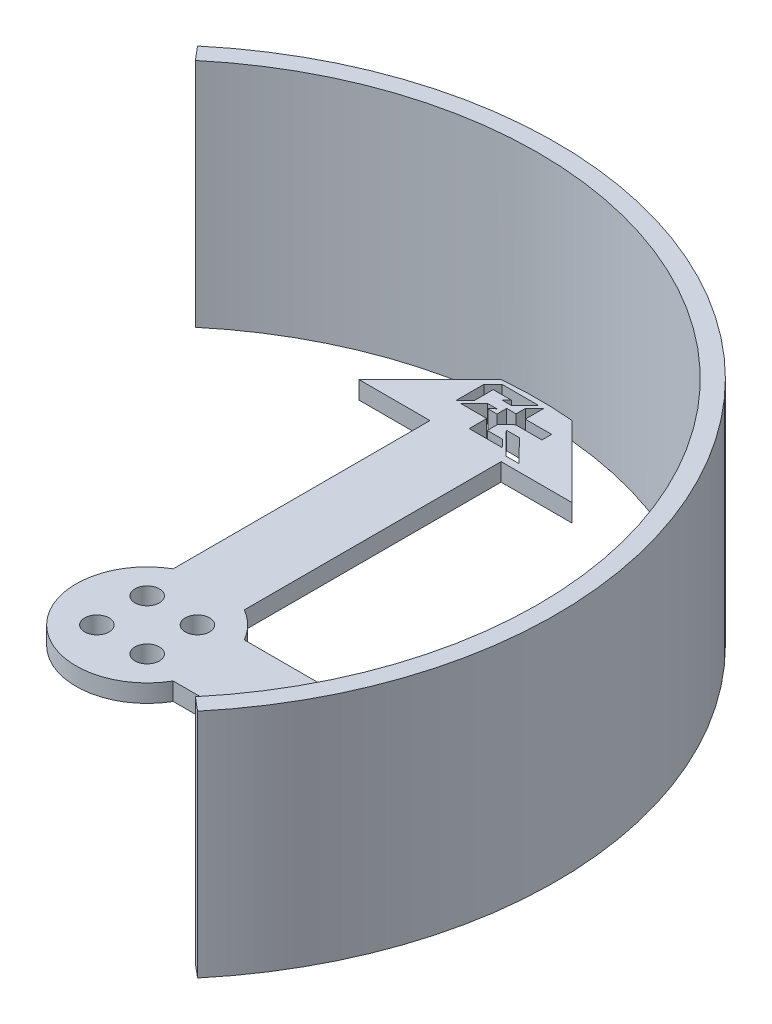
SolidWorks part; units mm, degrees
material "ABS"
ref_plane "Front Plane" through (0, 0, 0) normal (0, 0, 1) x (1, 0, 0)
ref_plane "Top Plane" through (0, 0, 0) normal (0, 1, 0) x (1, 0, 0)
ref_plane "Right Plane" through (0, 0, 0) normal (1, 0, 0) x (0, 0, -1)
sketch "Sketch1" plane through (0, 0, 0) normal (0, 1, 0) x (1, 0, 0)
  line L0 (-6.35, -6.35) -> (-6.35, 69.85)
  line L1 (-6.35, -6.35) -> (69.85, -6.35)
  line L2 (6.35, 69.85) -> (6.35, 6.35)
  line L3 (6.35, 6.35) -> (69.85, 6.35)
  line L4 (69.85, -6.35) -> (69.85, 6.35)
  line L5 (-6.35, 69.85) -> (6.35, 69.85)
  line L6 (69.85, -6.35) -> (70.6956, -0.6017)
  dimension "D1" = 63.5
  dimension "D2" = 63.5
  dimension "D3" = 12.7
  dimension "D4" = 6.35
  dimension "D5" = 12.7
  dimension "D6" = 6.35
extrude "Boss-Extrude1" add sketch "Sketch1" along normal blind 3.175 contours L5 L0 L1 L4 L3 L2 | L1 L0 L5 L2 L3 L4 region at (-5.2724, 0, -31.75)
sketch "Sketch2" plane through (0, 3.175, 0) normal (0, 1, 0) x (1, 0, 0)
  line L0 (0, 69.85) -> (0, 0) construction
  line L1 (0, 0) -> (-44.8987, 53.5082) construction
  line L2 (-46.9396, 55.9404) -> (-44.8987, 53.5082)
  line L3 (53.5082, -44.8987) -> (55.9404, -46.9396)
  arc A0 (-44.8987, 53.5082) -> (53.5082, -44.8987) centre (0, 0) cw
  arc A1 (-46.9396, 55.9404) -> (55.9404, -46.9396) centre (0, 0) cw
  dimension "D1" = 69.85
  dimension "D2" = 170
  dimension "D3" = 40
  dimension "D4" = 170
  dimension "D5" = 73.025
  dimension "D6" = 0
extrude "Boss-Extrude4" add sketch "Sketch2" along normal blind 38.1 and the other way blind 3.175
sketch "Sketch3" plane through (0, 3.175, 0) normal (0, 1, 0) x (1, 0, 0)
  circle A0 centre (0, 0) radius 12.7
  dimension "D1" = 25.4
extrude "Boss-Extrude5" add sketch "Sketch3" against normal blind 3.175
sketch "Sketch4" plane through (0, 3.175, 0) normal (0, 1, 0) x (1, 0, 0)
  line L0 (8.9803, 8.9803) -> (-8.9803, -8.9803) construction
  line L1 (-8.9803, 8.9803) -> (8.9803, -8.9803) construction
  arc A0 (10.9985, 6.35) -> (6.35, 10.9985) centre (0, 0) ccw construction
  arc A1 (-6.35, 10.9985) -> (10.9985, -6.35) centre (0, 0) ccw construction
  circle A2 centre (4.4901, 4.4901) radius 2.1828
  circle A3 centre (4.4901, -4.4901) radius 2.1828
  circle A4 centre (-4.4901, -4.4901) radius 2.1828
  circle A5 centre (-4.4901, 4.4901) radius 2.1828
  point P22 (0, 0)
  dimension "D3" = 4.3656
  dimension "D4" = 6.35
  dimension "D1" = 90
  dimension "D2" = 0
  dimension "D6" = 0
  dimension "D7" = 0
  dimension "D5" = 4
extrude "Cut-Extrude1" cut sketch "Sketch4" against normal through all
sketch "Sketch5" plane through (0, 3.175, 0) normal (0, 1, 0) x (1, 0, 0)
  line L0 (149.953, 323.8764) -> (789.953, 323.8764) construction
sketch "Sketch6" plane through (0, 3.175, 0) normal (0, 1, 0) x (1, 0, 0)
  line L0 (-6.35, 69.5608) -> (6.35, 69.5608)
  line L1 (6.35, 69.5608) -> (19.05, 56.8608)
  line L2 (19.05, 56.8608) -> (-19.05, 56.8608)
  line L3 (-19.05, 56.8608) -> (-6.35, 69.5608)
  line L4 (-8.9803, -8.9803) -> (8.9803, 8.9803) construction
  line L5 (69.5608, 6.35) -> (56.8608, 19.05)
  line L6 (69.5608, -6.35) -> (69.5608, 6.35)
  line L7 (56.8608, -19.05) -> (69.5608, -6.35)
  line L8 (56.8608, 19.05) -> (56.8608, -19.05)
  arc A0 (-6.35, 10.9985) -> (10.9985, -6.35) centre (0, 0) ccw construction
  arc A1 (10.9985, 6.35) -> (6.35, 10.9985) centre (0, 0) ccw construction
  dimension "D1" = 38.1
  dimension "D2" = 45
  dimension "D3" = 45
extrude "Boss-Extrude6" add sketch "Sketch6" against normal blind 3.175
sketch "Sketch7" plane through (0, 3.175, 0) normal (0, 1, 0) x (1, 0, 0)
  line L0 (151.1655, 325.7659) -> (791.1655, 325.7659) construction
  line L1 (-7.1332, 67.2918) -> (-7.1332, 62.2499)
  line L2 (-7.1332, 62.2499) -> (-5.4899, 63.8932)
  line L3 (-5.4899, 63.8932) -> (-5.4899, 67.2918)
  line L4 (-5.4899, 67.2918) -> (-2.2034, 67.2918)
  line L5 (-2.2034, 67.2918) -> (-3.025, 66.4702)
  line L6 (-3.025, 66.4702) -> (-1.3817, 66.4702)
  line L7 (-1.3817, 66.4702) -> (1.0459, 68.8978)
  line L8 (1.0459, 68.8978) -> (-5.4899, 68.8978)
  line L9 (-5.4899, 68.8978) -> (-7.1332, 67.2918)
  line L10 (-6.3116, 62.2499) -> (-3.8467, 64.6588)
  line L11 (-3.8467, 64.6588) -> (-2.2034, 64.6588)
  line L12 (-2.2034, 64.6588) -> (-3.025, 63.8558)
  line L13 (-3.025, 63.8558) -> (-1.3817, 63.8558)
  line L14 (-1.3817, 63.8558) -> (-1.3817, 65.5925)
  line L15 (-1.3817, 65.5925) -> (0.2989, 65.5925)
  line L16 (0.2989, 65.5925) -> (0.2989, 67.2918)
  line L17 (0.2989, 67.2918) -> (1.9422, 68.8978)
  line L18 (1.9422, 68.8978) -> (1.9422, 65.5925)
  line L19 (1.9422, 65.5925) -> (6.648, 65.5925)
  line L20 (6.648, 65.5925) -> (6.648, 63.8558)
  line L21 (6.648, 63.8558) -> (1.9422, 63.8558)
  line L22 (1.9422, 63.8558) -> (0.2989, 62.2499)
  line L23 (0.2989, 62.2499) -> (0.2989, 60.4546)
  line L24 (0.2989, 60.4546) -> (2.9906, 60.4546)
  line L25 (2.9906, 60.4546) -> (4.2951, 59.1197)
  line L26 (4.2951, 59.1197) -> (-1.6058, 59.1197)
  line L27 (-1.6058, 59.1197) -> (-1.6058, 62.2499)
  line L28 (-1.6058, 62.2499) -> (-6.3116, 62.2499)
  line L29 (5.9108, 58.1512) -> (8.2471, 58.1512)
  line L30 (8.2471, 58.1512) -> (4.2951, 62.1951)
  line L31 (4.2951, 62.1951) -> (1.9422, 62.1951)
  line L32 (1.9422, 62.1951) -> (5.9108, 58.1512)
  line L33 (-8.9803, -8.9803) -> (8.9803, 8.9803) construction
  line L34 (67.2918, 7.1332) -> (62.2499, 7.1332)
  line L35 (62.2499, 7.1332) -> (63.8932, 5.4899)
  line L36 (63.8932, 5.4899) -> (67.2918, 5.4899)
  line L37 (67.2918, 5.4899) -> (67.2918, 2.2034)
  line L38 (67.2918, 2.2034) -> (66.4702, 3.025)
  line L39 (66.4702, 3.025) -> (66.4702, 1.3817)
  line L40 (66.4702, 1.3817) -> (68.8978, -1.0459)
  line L41 (68.8978, -1.0459) -> (68.8978, 5.4899)
  line L42 (68.8978, 5.4899) -> (67.2918, 7.1332)
  line L43 (62.2499, 6.3116) -> (64.6588, 3.8467)
  line L44 (64.6588, 3.8467) -> (64.6588, 2.2034)
  line L45 (64.6588, 2.2034) -> (63.8558, 3.025)
  line L46 (63.8558, 3.025) -> (63.8558, 1.3817)
  line L47 (63.8558, 1.3817) -> (65.5925, 1.3817)
  line L48 (65.5925, 1.3817) -> (65.5925, -0.2989)
  line L49 (65.5925, -0.2989) -> (67.2918, -0.2989)
  line L50 (67.2918, -0.2989) -> (68.8978, -1.9422)
  line L51 (68.8978, -1.9422) -> (65.5925, -1.9422)
  line L52 (65.5925, -1.9422) -> (65.5925, -6.648)
  line L53 (65.5925, -6.648) -> (63.8558, -6.648)
  line L54 (63.8558, -6.648) -> (63.8558, -1.9422)
  line L55 (63.8558, -1.9422) -> (62.2499, -0.2989)
  line L56 (62.2499, -0.2989) -> (60.4546, -0.2989)
  line L57 (60.4546, -0.2989) -> (60.4546, -2.9906)
  line L58 (60.4546, -2.9906) -> (59.1197, -4.2951)
  line L59 (59.1197, -4.2951) -> (59.1197, 1.6058)
  line L60 (59.1197, 1.6058) -> (62.2499, 1.6058)
  line L61 (62.2499, 1.6058) -> (62.2499, 6.3116)
  line L62 (58.1512, -5.9108) -> (58.1512, -8.2471)
  line L63 (58.1512, -8.2471) -> (62.1951, -4.2951)
  line L64 (62.1951, -4.2951) -> (62.1951, -1.9422)
  line L65 (62.1951, -1.9422) -> (58.1512, -5.9108)
  line L66 (0, 0) -> (5.9108, 58.1512) construction
  line L67 (0, 0) -> (58.1512, -5.9108) construction
  arc A0 (-6.35, 10.9985) -> (10.9985, -6.35) centre (0, 0) ccw construction
  arc A1 (10.9985, 6.35) -> (6.35, 10.9985) centre (0, 0) ccw construction
  dimension "D2" = 90
  dimension "D1" = 2
extrude "Cut-Extrude2" cut sketch "Sketch7" against normal through all
